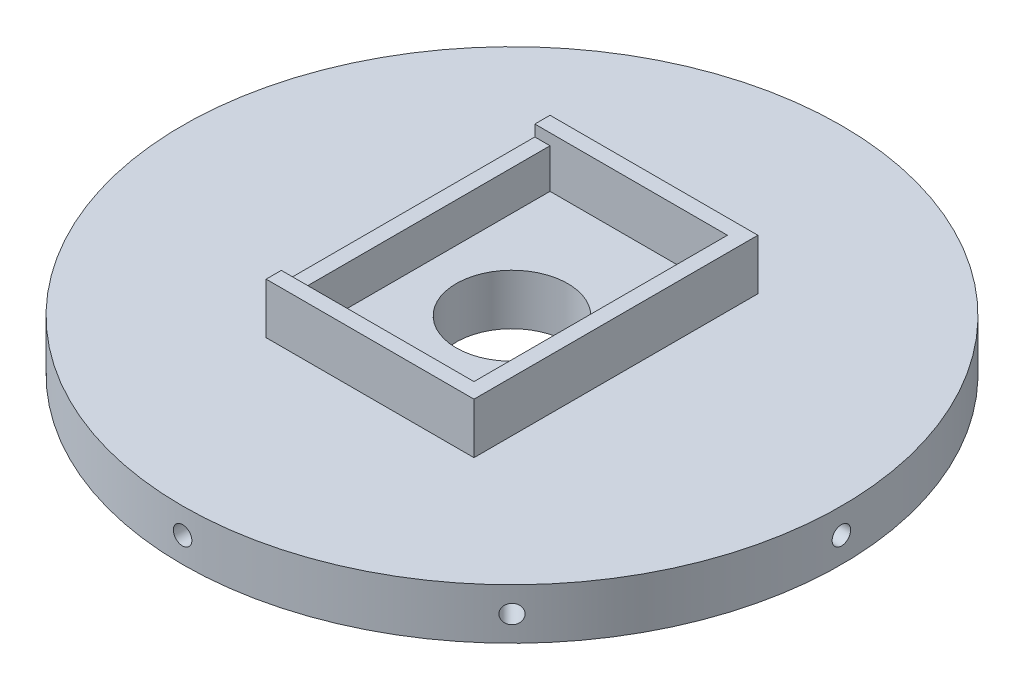
SolidWorks part; units mm, degrees
ref_plane "Front Plane" through (0, 0, 0) normal (0, 0, 1) x (1, 0, 0)
ref_plane "Top Plane" through (0, 0, 0) normal (0, 1, 0) x (1, 0, 0)
ref_plane "Right Plane" through (0, 0, 0) normal (1, 0, 0) x (0, 0, -1)
sketch "Sketch2" plane through (0, 0, 0) normal (0, 1, 0) x (1, 0, 0)
  line L0 (-17.5, -25) -> (-17.5, 25)
  line L1 (-17.5, 0) -> (17.5, 0)
  line L2 (0, 0) -> (0, 25)
  line L3 (-17.5, 25) -> (17.5, 25)
  line L4 (17.5, -25) -> (17.5, 25)
  line L5 (-17.5, -25) -> (17.5, -25)
  line L6 (-20.5, -28) -> (-20.5, 28)
  line L7 (-20.5, 0) -> (20.5, 0)
  line L8 (0, 0) -> (0, 28)
  line L9 (-20.5, 28) -> (20.5, 28)
  line L10 (20.5, -28) -> (20.5, 28)
  line L11 (-20.5, -28) -> (20.5, -28)
  line L12 (0, 28) -> (0, 65)
  circle A0 centre (0, 0) radius 65
  circle A1 centre (0, 0) radius 11
  dimension "D1" = 17.5
  dimension "D5" = 130
  dimension "D2" = 25
  dimension "D3" = 28
  dimension "D4" = 20.5
extrude "Boss-Extrude1" add sketch "Sketch2" along normal blind 20 contours L9 L6 L7 L0 L3 L8 | L0 L3 L4 L5 | L10 L9 L6 L11 region at (-19, 0, -0.347)
extrude "Boss-Extrude2" add sketch "Sketch2<3>" along normal blind 10 contours A0 L11 L6 L9 L10 region at (44.6619, 0, -44.6619)
sketch "Sketch2<3>" plane through (0, 0, 0) normal (0, 1, 0) x (1, 0, 0) same geometry as "Sketch2"
extrude "Boss-Extrude3" add sketch "Sketch2<4>" along normal blind 10 contours A1 L8 L3 L0 L1 | A1 L7 L4 L3 L8 | A1 L1 L0 L5 L4 L7 region at (0, 0, 14.6732) region at (-9.8826, 0, -14.6732) region at (9.8826, 0, -14.6732)
sketch "Sketch2<4>" plane through (0, 0, 0) normal (0, 1, 0) x (1, 0, 0) same geometry as "Sketch2"
ref_plane "Plane1" through (0, 0, 0) normal (0, 0, 1) x (1, 0, 0)
ref_plane "Plane2" through (0, 0, 0) normal (-1, 0, 0) x (0, 0, 1)
ref_plane "Plane3" through (0, 0, 0) normal (0.7071, 0, 0.7071) x (0.7071, 0, -0.7071)
sketch "Sketch10" plane through (-20.5, 0, 0) normal (-1, 0, 0) x (0, 0, 1)
  line L0 (28, 20) -> (-28, 20) construction
  line L1 (25, 20) -> (-25, 20)
  line L2 (25, 20) -> (25, 17.788)
  line L3 (25, 17.788) -> (-25, 17.788)
  line L4 (-25, 20) -> (-25, 17.788)
  line L5 (25, 20) -> (25, 10) construction
  line L6 (-25, 20) -> (-25, 10) construction
extrude "Cut-Extrude1" cut sketch "Sketch10" against normal blind 10
sketch "Sketch12" plane through (0, 0, 0) normal (0, 0, 1) x (1, 0, 0)
  circle A0 centre (0, 5) radius 1.825
  dimension "D1" = 5
extrude "Cut-Extrude2" cut sketch "Sketch12" against normal blind 11 from offset 65
sketch "Sketch13" [suppressed] plane through (0, 0, 0) normal (0, 0, 1) x (1, 0, 0)
  line L0 (0, 0) -> (0, 45.7901)
pattern_circular "CirPattern1" count 8 over 360 about axis through (0, 0, 0) along (0, 1, 0) of "Cut-Extrude2" reverse direction yes
